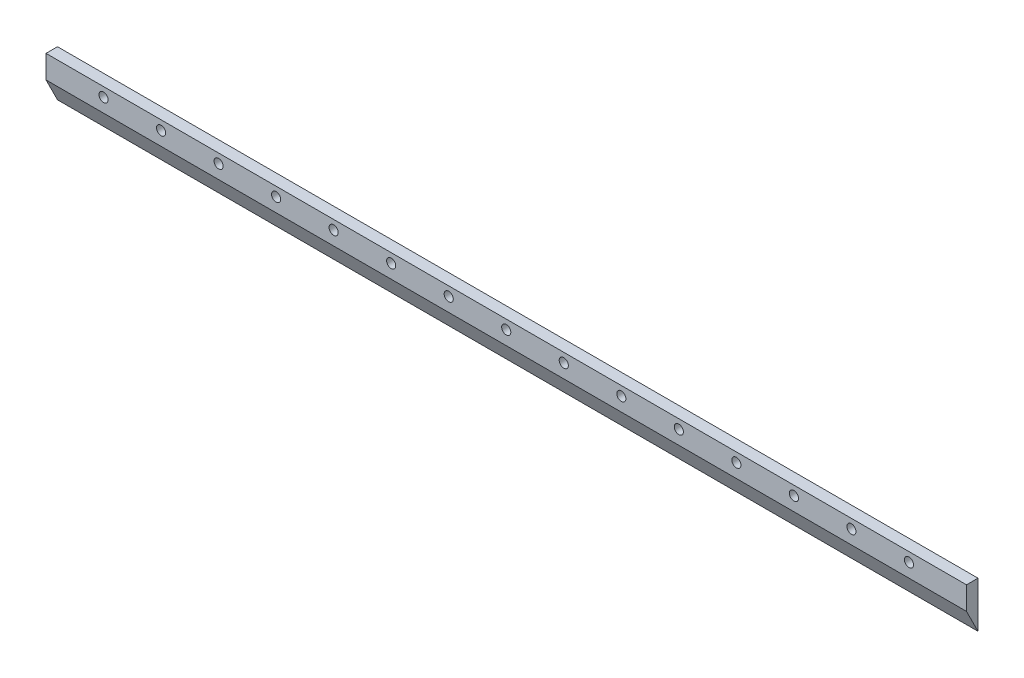
SolidWorks part; units mm, degrees
ref_plane "Alzado" through (0, 0, 0) normal (0, 0, 1) x (1, 0, 0)
ref_plane "Planta" through (0, 0, 0) normal (0, 1, 0) x (1, 0, 0)
ref_plane "Vista lateral" through (0, 0, 0) normal (1, 0, 0) x (0, 0, -1)
sketch "Croquis1" plane through (0, 0, 0) normal (0, 0, 1) x (1, 0, 0)
  line L1 (-400, -20) -> (400, -20)
  line L2 (-400, -20) -> (-400, 20)
  line L3 (-400, 20) -> (400, 20)
  line L4 (400, -20) -> (400, 20)
  line L5 (-400, -20) -> (400, 20) construction
  line L6 (-400, 20) -> (400, -20) construction
  point P0 (0, 0)
  dimension "D1" = 800
  dimension "D2" = 40
extrude "Saliente-Extruir1" add sketch "Croquis1" along normal blind 10
sketch "Croquis2" plane through (400, 0, 0) normal (1, 0, 0) x (0, 0, -1)
  line L0 (0, -20) -> (-10, 0)
  line L1 (-10, -20) -> (-10, 20) construction
  line L2 (-10, 0) -> (0, 0)
  line L3 (0, 0) -> (0, -20)
  line L8 (0, -20) -> (0, 20)
  line L9 (0, 20) -> (-10, 20)
  line L10 (-10, 20) -> (-10, -20)
  line L11 (-10, -20) -> (0, -20)
  line L12 (0, -20) -> (0, 20)
  line L13 (0, 20) -> (-10, 20)
  line L14 (-10, 20) -> (-10, -20)
  line L15 (-10, -20) -> (0, -20)
  line M7 (-10, 20) -> (-10, -20)
  line M8 (-10, -20) -> (0, -20)
  dimension "D1" = 0
extrude "Cortar-Extruir1" cut sketch "Croquis2" against normal through all contours L0 M8 M7 region at (400, -13.3333, 6.6667)
sketch "Croquis3" plane through (0, 0, 0) normal (0, 0, -1) x (-1, 0, 0)
  line L0 (449.2914, 0) -> (-432.142, 0) construction
  line L1 (-432.142, 12) -> (449.2914, 12) construction
  line L3 (-400, -20) -> (-400, 20) construction
  line L4 (-350, 12) -> (-300, 12) construction
  circle A0 centre (-350, 12) radius 3.9688
  circle A1 centre (-300, 12) radius 3.9688
  circle A2 centre (-250, 12) radius 3.9688
  circle A3 centre (-200, 12) radius 3.9688
  circle A4 centre (-150, 12) radius 3.9688
  circle A5 centre (-100, 12) radius 3.9688
  circle A6 centre (-50, 12) radius 3.9688
  circle A7 centre (0, 12) radius 3.9688
  circle A8 centre (50, 12) radius 3.9688
  circle A9 centre (100, 12) radius 3.9688
  circle A10 centre (150, 12) radius 3.9688
  circle A11 centre (200, 12) radius 3.9688
  circle A12 centre (250, 12) radius 3.9688
  circle A13 centre (300, 12) radius 3.9688
  circle A14 centre (350, 12) radius 3.9688
  dimension "D3" = 7.9375
  dimension "D1" = 12
  dimension "D2" = 50
  dimension "D5" = 50
  dimension "D4" = 15
extrude "Cortar-Extruir2" cut sketch "Croquis3" against normal blind 10
